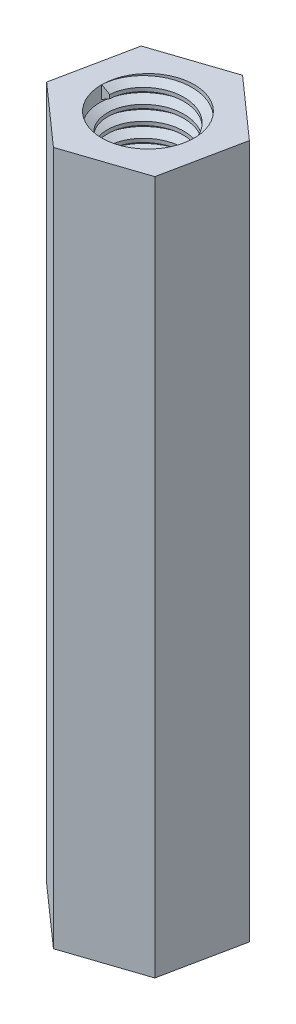
SolidWorks part; units mm, degrees
ref_plane "前视基准面" through (0, 0, 0) normal (0, 0, 1) x (1, 0, 0)
ref_plane "上视基准面" through (0, 0, 0) normal (0, 1, 0) x (1, 0, 0)
ref_plane "右视基准面" through (0, 0, 0) normal (1, 0, 0) x (0, 0, -1)
other "Configuration Table"
sketch "草图1" plane through (0, 0, 0) normal (0, 1, 0) x (1, 0, 0)
  line L1 (1.296, -1.1491) -> (1.6431, 0.5478)
  line L2 (1.6431, 0.5478) -> (0.3472, 1.6969)
  line L3 (0.3472, 1.6969) -> (-1.296, 1.1491)
  line L4 (-1.296, 1.1491) -> (-1.6431, -0.5478)
  line L5 (-1.6431, -0.5478) -> (-0.3472, -1.6969)
  line L6 (-0.3472, -1.6969) -> (1.296, -1.1491)
  circle A0 centre (0, 0) radius 1.5 construction
extrude "凸台-拉伸1" add sketch "草图1" along normal blind 15
sketch "草图2" plane through (0, 15, 0) normal (0, 1, 0) x (1, 0, 0)
  circle A0 centre (0, 0) radius 1
extrude "切除-拉伸1" cut sketch "草图2" against normal through all
thread "螺纹线1" pitch 0.3175 method extrude profile "螺纹线轮廓1" start angle 0, offset 0, length 14.7, pitch 0.3175, diameter 2
ref_plane "基准面1" through (-1, 15, 0) normal (0, 0, 1) x (-1, 0, 0)
sketch "螺纹线轮廓1" plane through (-1, 15, 0) normal (0, 0, 1) x (-1, 0, 0)
  line L0 (0, 0) -> (0, 0.3175) construction
  line L11 (0, 0) -> (0, 0.2778)
  line L12 (0, 0.2778) -> (-0.1719, 0.1786)
  line L13 (-0.1719, 0.1786) -> (-0.1719, 0.0992)
  line L15 (-0.1719, 0.0992) -> (0, 0)
  line L17 (-0.1719, 0.1389) -> (0, 0.1389) construction
  point P2 (0, 0)
  dimension "Pitch" = 0.3175
  dimension "Profile_Angle" = 60
  dimension "Profile_Land" = 0.0794
  dimension "Profile_Height" = 0.1719
